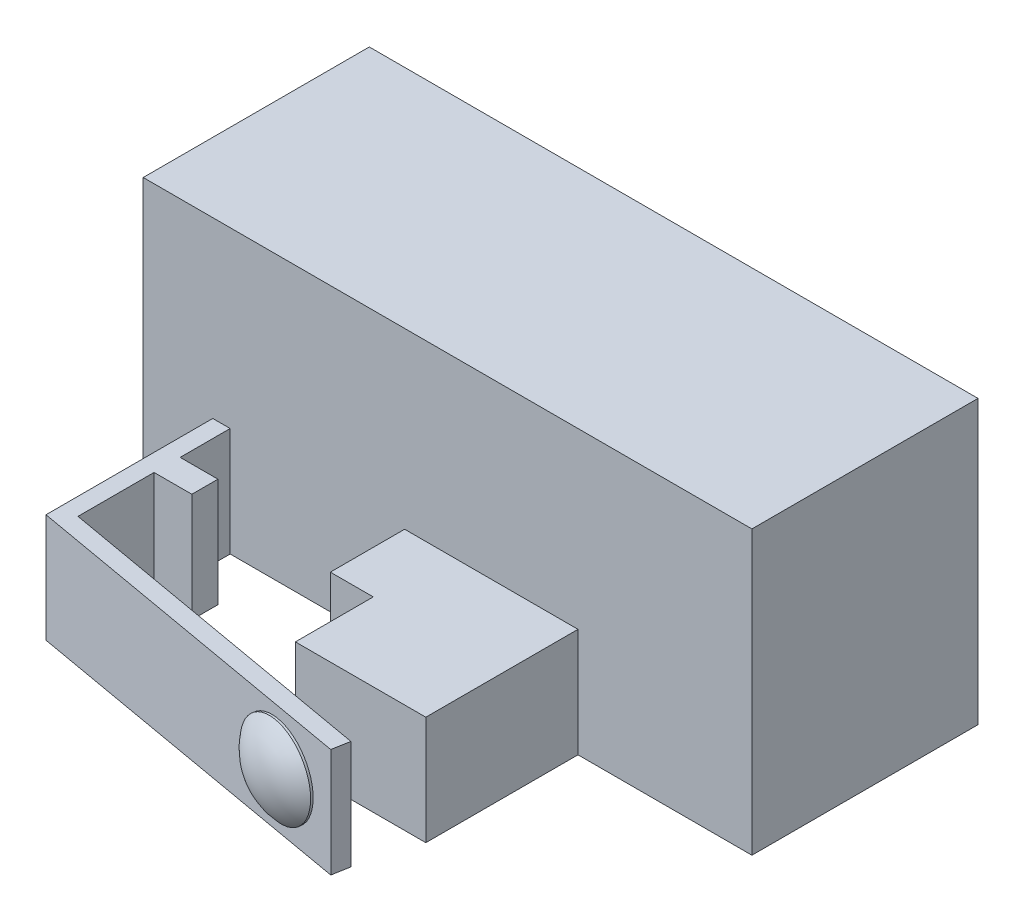
SolidWorks part; units mm, degrees
ref_plane "Front Plane" through (0, 0, 0) normal (0, 0, 1) x (1, 0, 0)
ref_plane "Top Plane" through (0, 0, 0) normal (0, 1, 0) x (1, 0, 0)
ref_plane "Right Plane" through (0, 0, 0) normal (1, 0, 0) x (0, 0, -1)
sketch "Sketch1" plane through (0, 0, 0) normal (0, 0, 1) x (1, 0, 0)
  line L0 (-16.1226, -15.8774) -> (-12.1226, -15.8774)
  line L1 (-12.1226, -15.8774) -> (-12.1226, -6.8774)
  line L2 (-12.1226, -6.8774) -> (7.8774, -6.8774)
  line L3 (7.8774, -6.8774) -> (7.8774, -15.8774)
  line L4 (7.8774, -15.8774) -> (11.8774, -15.8774)
  line L5 (11.8774, -15.8774) -> (11.8774, -2.8774)
  line L6 (11.8774, -2.8774) -> (-16.1226, -2.8774)
  line L7 (-16.1226, -2.8774) -> (-16.1226, -15.8774)
  dimension "D1" = 20
  dimension "D2" = 9
  dimension "D3" = 9
  dimension "D4" = 13
  dimension "D5" = 4
  dimension "D6" = 4
extrude "Boss-Extrude1" add sketch "Sketch1" along normal blind 9.6
sketch "Sketch2" plane through (0, 0, 9.6) normal (0, 0, 1) x (1, 0, 0)
  line L1 (-16.1226, -2.8774) -> (11.8774, -2.8774)
  line L2 (-16.1226, -2.8774) -> (-16.1226, -15.8774)
  line L3 (-16.1226, -15.8774) -> (11.8774, -15.8774)
  line L4 (11.8774, -2.8774) -> (11.8774, -15.8774)
extrude "Boss-Extrude2" add sketch "Sketch2" along normal blind 0.8
sketch "Sketch3" plane through (0, -15.8774, 0) normal (0, -1, 0) x (1, 0, 0)
  line L3 (-4.0969, 10.4) -> (3.8774, 10.4)
  line L5 (-16.1226, 10.4) -> (11.8774, 10.4) construction
  line L6 (3.8774, 10.4) -> (3.8774, 17.4)
  line L7 (3.8774, 17.4) -> (-2.1226, 17.4)
  line L12 (-12.1226, 17.4) -> (3.1191, 20.0875)
  line L13 (3.1191, 20.0875) -> (2.9802, 20.8754)
  line L19 (2.9802, 20.8754) -> (-12.9226, 18.0713)
  line L20 (-12.9226, 18.0713) -> (-12.9226, 13.9618)
  line L25 (-12.9226, 10.4) -> (-12.9226, 13.9618)
  line L31 (-12.1226, 17.4) -> (-12.1226, 13.9)
  line L32 (-12.1226, 13.9) -> (-10.3845, 13.9)
  line L33 (-10.3845, 13.9) -> (-10.3845, 12.7)
  line L34 (-10.3845, 12.7) -> (-12.1226, 12.7)
  line L35 (-12.1226, 12.7) -> (-12.1226, 10.4)
  line L36 (-12.1226, 10.4) -> (-12.9226, 10.4)
  line L37 (-4.0969, 10.4) -> (-4.0969, 13.8175)
  line L38 (-4.0969, 13.8175) -> (-2.1226, 13.8175)
  line L39 (-2.1226, 13.8175) -> (-2.1226, 17.4)
  dimension "D7" = 0.8
  dimension "D8" = 0.8
  dimension "D3" = 3.5
  dimension "D1" = 6
  dimension "D2" = 7
  dimension "D4" = 1.2
  dimension "D5" = 10
  dimension "D6" = 0.8
  dimension "D11" = 16.1482
  dimension "D12" = 260
extrude "Boss-Extrude3" add sketch "Sketch3" against normal blind 5
sketch "Sketch4" plane through (-3.48, 0, 19.7363) normal (-0.1736, 0, 0.9848) x (0.9848, 0, 0.1736)
  line L0 (6.5599, -10.8774) -> (6.5599, -15.8774) construction
  line L1 (6.5599, -15.8774) -> (-9.5883, -15.8774) construction
  circle A0 centre (3.5599, -13.3774) radius 2
  dimension "D1" = 4
  dimension "D2" = 3
  dimension "D3" = 2.5
extrude "Boss-Extrude4" add sketch "Sketch4" along normal blind 0.1
dome "Dome1" faces to dome 1 distance 0.8 reverse direction no elliptical dome no face at (1.978, -13.3774, 20.8002) parameters "D1"=0.8
